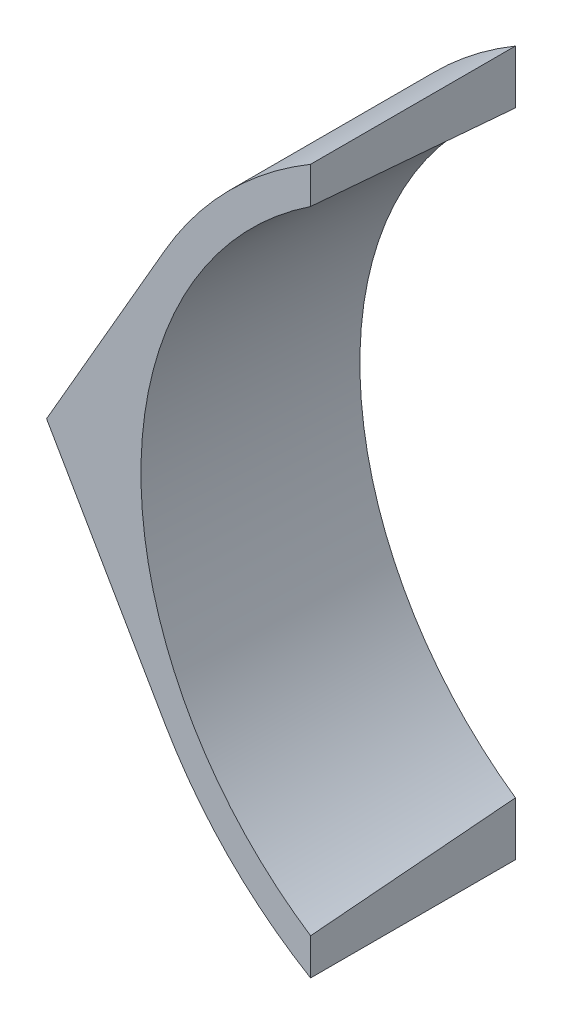
SolidWorks part; units mm, degrees
ref_plane "前视基准面" through (0, 0, 0) normal (0, 0, 1) x (1, 0, 0)
ref_plane "上视基准面" through (0, 0, 0) normal (0, 1, 0) x (1, 0, 0)
ref_plane "右视基准面" through (0, 0, 0) normal (1, 0, 0) x (0, 0, -1)
other "Configuration Table"
sketch "草图1" plane through (0, 0, 0) normal (0, 0, 1) x (1, 0, 0)
  line L0 (12.1109, 16.0114) -> (0, 0)
  line L1 (0, 0) -> (12.1109, -16.0114)
  line L2 (-24.6267, 0) -> (6.7081, 0) construction
  line L3 (-0.7756, 0) -> (12.1109, 22.32)
  line L4 (-0.7756, 0) -> (12.1109, -22.32)
  line L5 (12.1109, 22.32) -> (12.1109, -22.32)
  circle A0 centre (22.3184, 0) radius 17.8
  circle A1 centre (22.3184, 0) radius 20
  dimension "D1" = 35.6
  dimension "D3" = 40
  dimension "D2" = 120
  dimension "D4" = 44.64
extrude "凸台-拉伸1" add sketch "草图1" along normal blind 10 contours L2 L4 A1 L1 | L1 A1 L5 | L2 A1 L1 A0 | A0 L1 L5 | L2 L1 A1 | L0 L2 A1 | L3 L2 L0 A1 | A1 L2 A0 L0 | L5 A1 L0 | A0 L5 L0 region at (11.0651, 14.1901, 0) region at (7.2339, 11.067, 0) region at (4.04, 3.2822, 0) region at (1.6102, 1.1285, 0) region at (1.6678, 3.3723, 0) region at (4.04, -3.2822, 0) region at (11.0651, -14.1901, 0) region at (1.6102, -1.1285, 0) region at (1.6678, -3.3723, 0) region at (7.2339, -11.067, 0)
ref_axis "基准轴1" through (22.3184, 0, 10) along (0, 0, -1)
ref_plane "基准面1" through (0, 0, 0) normal (0, -1, 0) x (0, 0, -1)
sketch "草图2" plane through (0, 0, 0) normal (0, -1, 0) x (0, 0, -1)
  line L0 (-18.3061, 22.3184) -> (6.0968, 22.3184) construction
  line L1 (-10, 22.3184) -> (0, 22.3184) construction
  line L2 (0, 22.3184) -> (0, 4.5184)
  line L3 (0, 4.9979) -> (0, 12.1109) construction
  line L4 (0, 4.5184) -> (-10, 3.8314)
  line L5 (-10, -0.7756) -> (-10, 4.9979) construction
  line L6 (-10, 3.8314) -> (-10, 22.3184)
  line L7 (-10, 22.3184) -> (0, 22.3184)
  line L8 (0, -0.7756) -> (0, 4.9979) construction
  dimension "D1" = 17.8
  dimension "D2" = 3.93
revolve "切除-旋转1" cut sketch "草图2" angle 360 about L0
